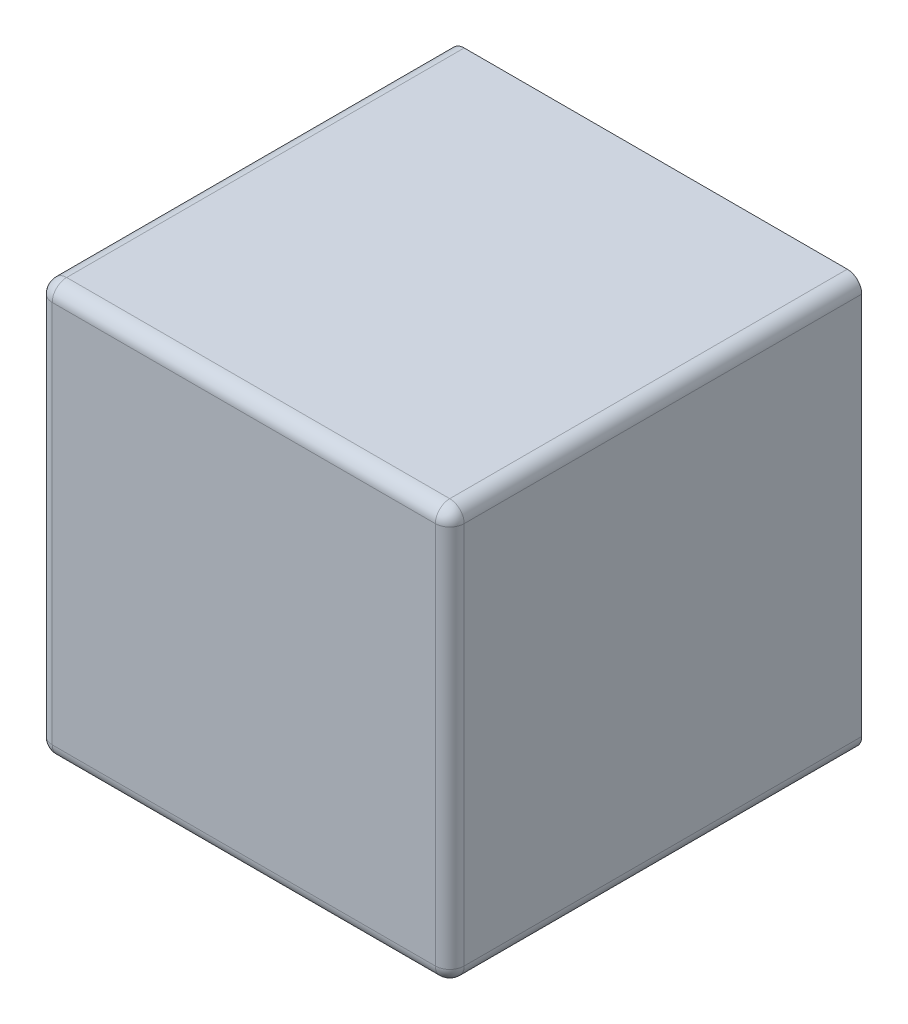
SolidWorks part; units mm, degrees
ref_plane "Plano frontal" through (0, 0, 0) normal (0, 0, 1) x (1, 0, 0)
ref_plane "Plano superior" through (0, 0, 0) normal (0, 1, 0) x (1, 0, 0)
ref_plane "Plano direito" through (0, 0, 0) normal (1, 0, 0) x (0, 0, -1)
sketch "Esboço1" plane through (0, 0, 0) normal (0, 0, 1) x (1, 0, 0)
  line L1 (0, 0) -> (200, 0)
  line L2 (0, 0) -> (0, 200)
  line L3 (0, 200) -> (200, 200)
  line L4 (200, 0) -> (200, 200)
  dimension "D1" = 200
  dimension "D2" = 200
extrude "Ressalto-extrusão2" add sketch "Esboço1" along normal blind 200 contours L2 L3 L4 L1
sketch "Esboço4" plane through (0, 0, 0) normal (0, 0, -1) x (-1, 0, 0)
  line L0 (0, 0) -> (-200, 0) construction
  line L1 (-190, 10) -> (-98.9473, 10)
  line L2 (-190, 10) -> (-190, 190)
  line L3 (-190, 190) -> (-98.9473, 190)
  line L4 (-98.9473, 10) -> (-98.9473, 190)
  line L5 (-93.9473, 10) -> (-10, 10)
  line L6 (-93.9473, 10) -> (-93.9473, 78.6647)
  line L7 (-93.9473, 78.6647) -> (-10, 78.6647)
  line L8 (-10, 10) -> (-10, 78.6647)
  line L9 (-93.9473, 190) -> (-10, 190)
  line L10 (-93.9473, 190) -> (-93.9473, 83.6647)
  line L11 (-93.9473, 83.6647) -> (-10, 83.6647)
  line L12 (-10, 190) -> (-10, 83.6647)
  line L13 (0, 0) -> (0, 200) construction
  line L14 (0, 200) -> (-200, 200) construction
  line L15 (-200, 0) -> (-200, 200) construction
  dimension "D1" = 10
  dimension "D2" = 10
  dimension "D3" = 10
  dimension "D4" = 10
  dimension "D5" = 10
  dimension "D6" = 10
  dimension "D7" = 10
  dimension "D8" = 5
  dimension "D9" = 5
  dimension "D10" = 5
extrude "Corte-extrusão2" cut sketch "Esboço4" against normal blind 190
fillet "Filete2" radius 7 4 edges at (0, 200, 100) (200, 200, 100) (0, 0, 100) (200, 0, 100)
fillet "Filete3" radius 7 10 edges at (93.9473, 78.6647, 95) (190, 190, 95) (190, 10, 95) (93.9473, 10, 95) (98.9473, 10, 95) (10, 83.6647, 95) (10, 190, 95) (98.9473, 190, 95) (10, 78.6647, 95) (10, 10, 95)
fillet "Filete4" radius 7 22 edges at (100.9975, 187.9497, 190) (98.9473, 100, 190) (100.9975, 12.0503, 190) (144.4736, 10, 190) (187.9497, 12.0503, 190) (190, 100, 190) (187.9497, 187.9497, 190) (144.4736, 190, 190) (93.9473, 136.8323, 190) (55.4736, 190, 190) (12.0503, 187.9497, 190) (10, 136.8323, 190) (12.0503, 85.7149, 190) (55.4736, 83.6647, 190) (12.0503, 76.6144, 190) (10, 44.3323, 190) (12.0503, 12.0503, 190) (51.9736, 10, 190) (91.897, 12.0503, 190) (93.9473, 44.3323, 190) (91.897, 76.6144, 190) (51.9736, 78.6647, 190)
fillet "Filete5" radius 7 8 edges at (197.9497, 197.9497, 200) (200, 100, 200) (197.9497, 2.0503, 200) (100, 0, 200) (2.0503, 2.0503, 200) (0, 100, 200) (2.0503, 197.9497, 200) (100, 200, 200)
fillet "Filete6" radius 7 4 edges at (91.897, 187.9497, 187.9497) (91.897, 85.7149, 187.9497) (93.9473, 190, 91.5) (93.9473, 83.6647, 91.5)
sketch "Esboço5" plane through (0, 83.6647, 0) normal (0, 1, 0) x (1, 0, 0)
  line L0 (86.9473, 0) -> (17, 0) construction
  circle A0 centre (53.7535, -10) radius 5
  dimension "D1" = 10
  dimension "D2" = 10
extrude "Corte-extrusão3" cut sketch "Esboço5" against normal blind 10
sketch "Esboço6" plane through (0, 0, 0) normal (-1, 0, 0) x (0, 0, 1)
  line L1 (193, 7) -> (193, 193) construction
  circle A0 centre (173, 172.4654) radius 10
  dimension "D1" = 20
  dimension "D2" = 20
extrude "Corte-extrusão4" cut sketch "Esboço6" against normal blind 10
